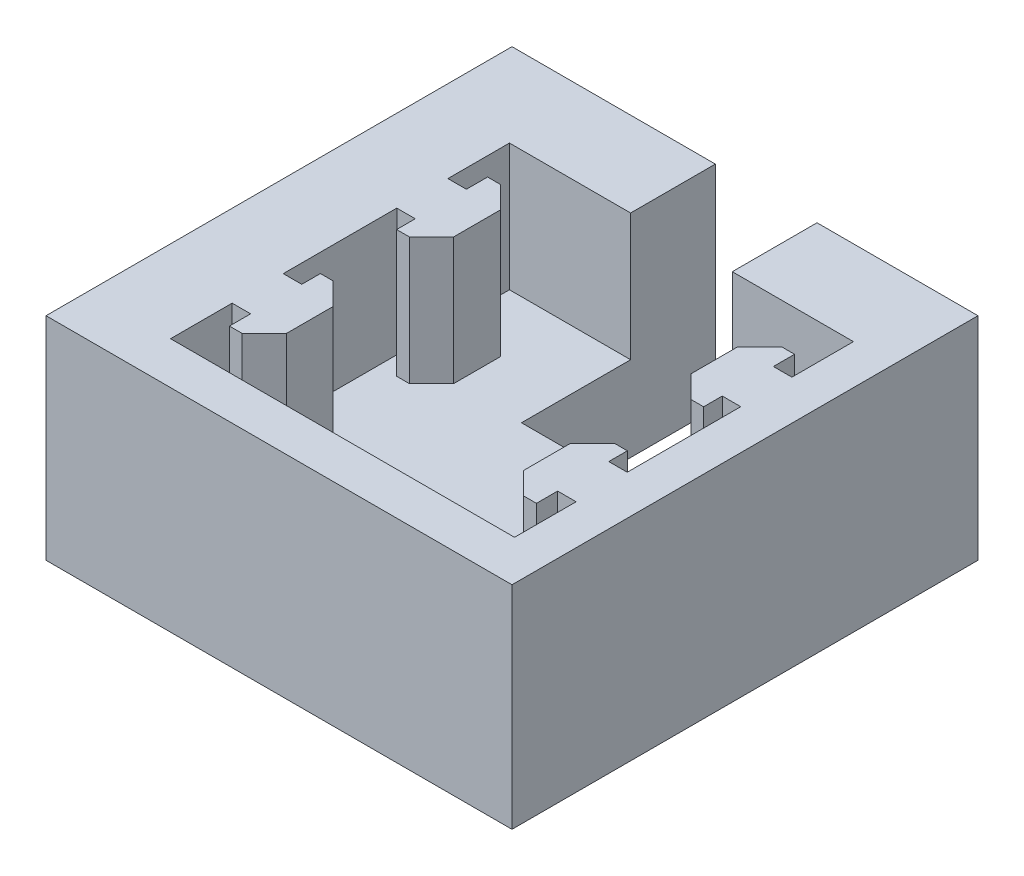
SolidWorks part; units mm, degrees
ref_plane "Front Plane" through (0, 0, 0) normal (0, 0, 1) x (1, 0, 0)
ref_plane "Top Plane" through (0, 0, 0) normal (0, 1, 0) x (1, 0, 0)
ref_plane "Right Plane" through (0, 0, 0) normal (1, 0, 0) x (0, 0, -1)
sketch "Sketch1" plane through (0, 0, 0) normal (0, 1, 0) x (1, 0, 0)
  line L1 (0, 0) -> (-55, 0)
  line L2 (0, 0) -> (0, -55)
  line L3 (0, -55) -> (-55, -55)
  line L4 (-55, 0) -> (-55, -55)
  dimension "D1" = 55
  dimension "D2" = 55
extrude "Boss-Extrude1" add sketch "Sketch1" along normal blind 10
sketch "Sketch2" plane through (0, 10, 0) normal (0, 1, 0) x (1, 0, 0)
  line L0 (-45.3163, -17.2674) -> (-43.1163, -17.2674)
  line L2 (-43.1163, -17.2674) -> (-43.1163, -14.7674)
  line L3 (-43.1163, -14.7674) -> (-41.6163, -14.7674)
  line L4 (-41.6163, -14.7674) -> (-39, -17.3837)
  line L5 (-39, -17.3837) -> (-39, -22.8837)
  line L6 (-39, -22.8837) -> (-41.6163, -25.5)
  line L7 (-41.6163, -25.5) -> (-43.1163, -25.5)
  line L8 (-43.1163, -25.5) -> (-43.1163, -23.3)
  line L9 (-43.1163, -23.3) -> (-45.3163, -23.3)
  line L10 (-45.3163, -23.3) -> (-45.3163, -17.2674)
  line L13 (-25, 0) -> (-25, -55) construction
  line L15 (-55, -30) -> (-3.9273, -30) construction
  line L18 (-6.8837, -23.3) -> (-4.6837, -23.3)
  line L19 (-6.8837, -25.5) -> (-6.8837, -23.3)
  line L20 (-8.3837, -25.5) -> (-6.8837, -25.5)
  line L21 (-11, -22.8837) -> (-8.3837, -25.5)
  line L22 (-11, -17.3837) -> (-11, -22.8837)
  line L23 (-8.3837, -14.7674) -> (-11, -17.3837)
  line L24 (-6.8837, -14.7674) -> (-8.3837, -14.7674)
  line L25 (-6.8837, -17.2674) -> (-6.8837, -14.7674)
  line L26 (-4.6837, -17.2674) -> (-6.8837, -17.2674)
  line L27 (-4.6837, -23.3) -> (-4.6837, -17.2674)
  line L28 (-43.1163, -36.7) -> (-45.3163, -36.7)
  line L29 (-43.1163, -34.5) -> (-43.1163, -36.7)
  line L30 (-41.6163, -34.5) -> (-43.1163, -34.5)
  line L31 (-39, -37.1163) -> (-41.6163, -34.5)
  line L32 (-39, -42.6163) -> (-39, -37.1163)
  line L33 (-41.6163, -45.2326) -> (-39, -42.6163)
  line L34 (-43.1163, -45.2326) -> (-41.6163, -45.2326)
  line L35 (-43.1163, -42.7326) -> (-43.1163, -45.2326)
  line L36 (-45.3163, -42.7326) -> (-43.1163, -42.7326)
  line L37 (-45.3163, -36.7) -> (-45.3163, -42.7326)
  line L38 (-6.8837, -34.5) -> (-6.8837, -36.7)
  line L39 (-8.3837, -34.5) -> (-6.8837, -34.5)
  line L40 (-11, -37.1163) -> (-8.3837, -34.5)
  line L41 (-11, -42.6163) -> (-11, -37.1163)
  line L42 (-8.3837, -45.2326) -> (-11, -42.6163)
  line L43 (-6.8837, -45.2326) -> (-8.3837, -45.2326)
  line L44 (-6.8837, -42.7326) -> (-6.8837, -45.2326)
  line L45 (-4.6837, -42.7326) -> (-6.8837, -42.7326)
  line L46 (-4.6837, -36.7) -> (-4.6837, -42.7326)
  line L47 (-6.8837, -36.7) -> (-4.6837, -36.7)
  line L48 (-55, -55) -> (0, -55) construction
  line L49 (-55, 0) -> (-55, -55) construction
  point P20 (-55, -27.5)
  point P52 (-27.5, -55)
  dimension "D1" = 2.2
  dimension "D2" = 2.2
  dimension "D3" = 2.5
  dimension "D4" = 2.2
  dimension "D5" = 3.7
  dimension "D6" = 3.7
  dimension "D7" = 5.5
  dimension "D8" = 1.5
  dimension "D9" = 1.5
  dimension "D10" = 4.5
  dimension "D11" = 14
  dimension "D12" = 0
  dimension "D13" = 2.5
  dimension "D14" = 2.5
  dimension "D15" = 0
extrude "Boss-Extrude3" add sketch "Sketch2" along normal blind 15
sketch "Sketch3" plane through (0, 10, 0) normal (0, 1, 0) x (1, 0, 0)
  line L0 (0, -55) -> (0, 0) construction
  line L1 (-55, 0) -> (0, 0)
  line L2 (-55, 0) -> (-55, -10)
  line L3 (-55, -10) -> (0, -10)
  line L4 (0, 0) -> (0, -10)
  line L6 (-55, -55) -> (0, -55)
  line L7 (-55, -55) -> (-55, -50)
  line L8 (-55, -50) -> (0, -50)
  line L9 (0, -55) -> (0, -50)
  line L10 (-55, -10) -> (-45.3, -10)
  line L11 (-55, -10) -> (-55, -50)
  line L12 (-55, -50) -> (-45.3, -50)
  line L13 (-45.3, -10) -> (-45.3, -50)
  line L14 (0, -10) -> (-4.7, -10)
  line L15 (0, -10) -> (0, -50)
  line L16 (0, -50) -> (-4.7, -50)
  line L17 (-4.7, -10) -> (-4.7, -50)
  line M15 (-45.3163, -42.7326) -> (-45.3163, -36.7)
  line M17 (-45.3163, -23.3) -> (-45.3163, -17.2674)
  line M27 (0, -55) -> (0, 0)
  line M28 (0, 0) -> (-55, 0)
  line M29 (-55, 0) -> (-55, -55)
  line M30 (-55, -55) -> (0, -55)
  line M39 (-4.6837, -17.2674) -> (-4.6837, -23.3)
  line M44 (-4.6837, -36.7) -> (-4.6837, -42.7326)
  dimension "D1" = 10
  dimension "D2" = 5
  dimension "D3" = 9.7
  dimension "D4" = 4.7
extrude "Boss-Extrude5" add sketch "Sketch3" along normal blind 15 contours L3 M29 M27 M28 | L13 L3 L8 M29 M15 M17 | L8 M29 M30 M27 | L3 L17 L8 M39 M44 M27 | L15 L14 L17 L16 | L2 L1 L4 L3 | L7 L6 L9 L8 | L11 L10 L13 L12 region at (-27.5, 10, 5) region at (-50.15, 10, 30) region at (-2.35, 10, 30) region at (-27.5, 10, 52.5)
sketch "Sketch7" plane through (0, 25, 0) normal (0, 1, 0) x (1, 0, 0)
  line L0 (-25, 0) -> (-25, -53.168) construction
  line L1 (-31, 0) -> (-19, 0)
  line L2 (-31, 0) -> (-31, -22.8837)
  line L3 (-31, -22.8837) -> (-19, -22.8837)
  line L4 (-19, 0) -> (-19, -22.8837)
  line L8 (0, 0) -> (-55, 0) construction
  point P8 (-27.5, 0)
  dimension "D1" = 12
  dimension "D2" = 6
  dimension "D3" = 0
  dimension "D4" = 0
  dimension "D5" = 2.5
  dimension "D6" = 0
extrude "Cut-Extrude3" cut sketch "Sketch7" against normal blind 45
sketch "Sketch8" plane through (0, 0, 0) normal (0, 0, -1) x (-1, 0, 0)
  line L0 (31, 0) -> (55, 0) construction
  line L1 (55, 25) -> (55, 0) construction
  circle A0 centre (50, 9) radius 2
  dimension "D1" = 4
  dimension "D2" = 9
  dimension "D3" = 5
extrude "Cut-Extrude4" cut sketch "Sketch8" against normal blind 7
sketch "Sketch9" plane through (0, 0, 0) normal (0, -1, 0) x (1, 0, 0)
  circle A0 centre (-40, 43) radius 2
  circle A1 centre (-50, 43) radius 2
  circle A2 centre (-40, 43) radius 2 construction
  circle A3 centre (-50, 43) radius 2 construction
  dimension "D1" = 4
  dimension "D2" = 4
  dimension "D3" = 0
  dimension "D4" = 0
  dimension "D5" = 0
  dimension "D6" = 0
extrude "Cut-Extrude5" cut sketch "Sketch9" against normal blind 7
